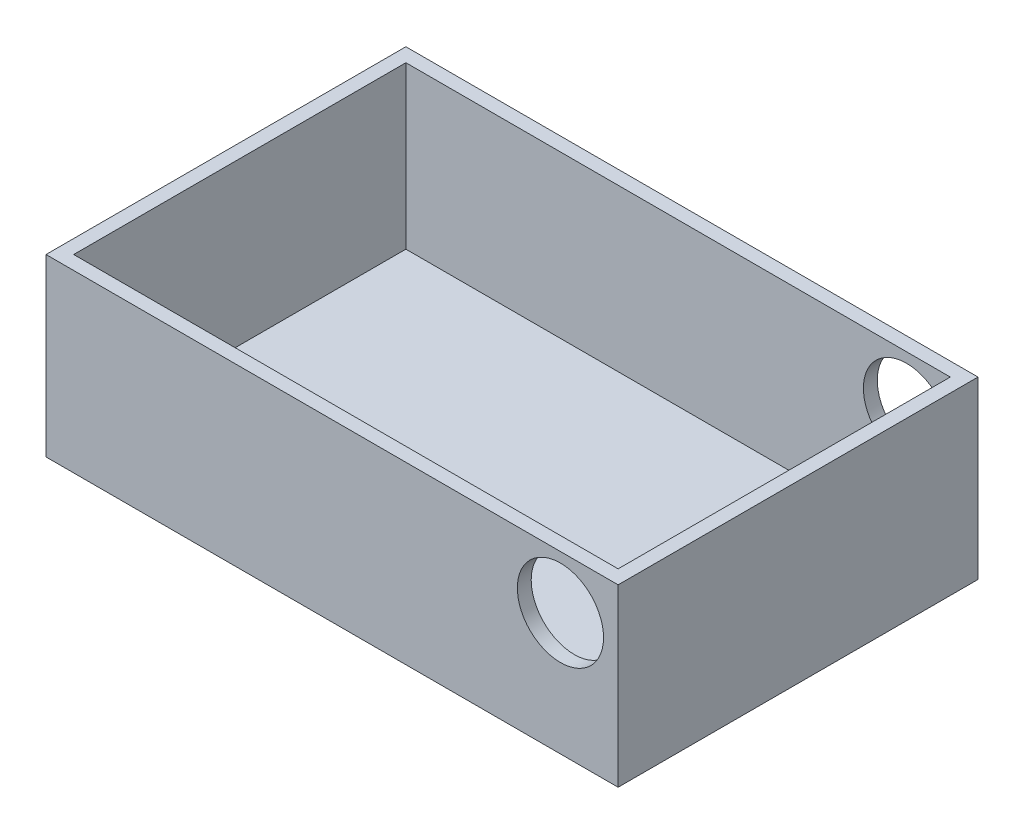
SolidWorks part; units mm, degrees
ref_plane "Front Plane" through (0, 0, 0) normal (0, 0, 1) x (1, 0, 0)
ref_plane "Top Plane" through (0, 0, 0) normal (0, 1, 0) x (1, 0, 0)
ref_plane "Right Plane" through (0, 0, 0) normal (1, 0, 0) x (0, 0, -1)
sketch "Sketch1" plane through (0, 0, 0) normal (0, 1, 0) x (1, 0, 0)
  line L1 (0, 0) -> (787.4, 0)
  line L2 (0, 0) -> (0, 495.3)
  line L3 (0, 495.3) -> (787.4, 495.3)
  line L4 (787.4, 0) -> (787.4, 495.3)
  dimension "D1" = 787.4
  dimension "D2" = 495.3
extrude "Boss-Extrude1" add sketch "Sketch1" along normal blind 241.3
shell "Shell1" thickness 19.05 removed face at (393.7, 241.3, -247.65)
sketch "Sketch2" plane through (0, 0, 0) normal (0, 0, 1) x (1, 0, 0)
  line L0 (0, 241.3) -> (0, 0) construction
  line L1 (0, 0) -> (787.4, 0) construction
  circle A0 centre (708.025, 168.275) radius 59.309
  dimension "D3" = 118.618
  dimension "D1" = 708.025
  dimension "D2" = 168.275
extrude "Cut-Extrude1" cut sketch "Sketch2" against normal through all
